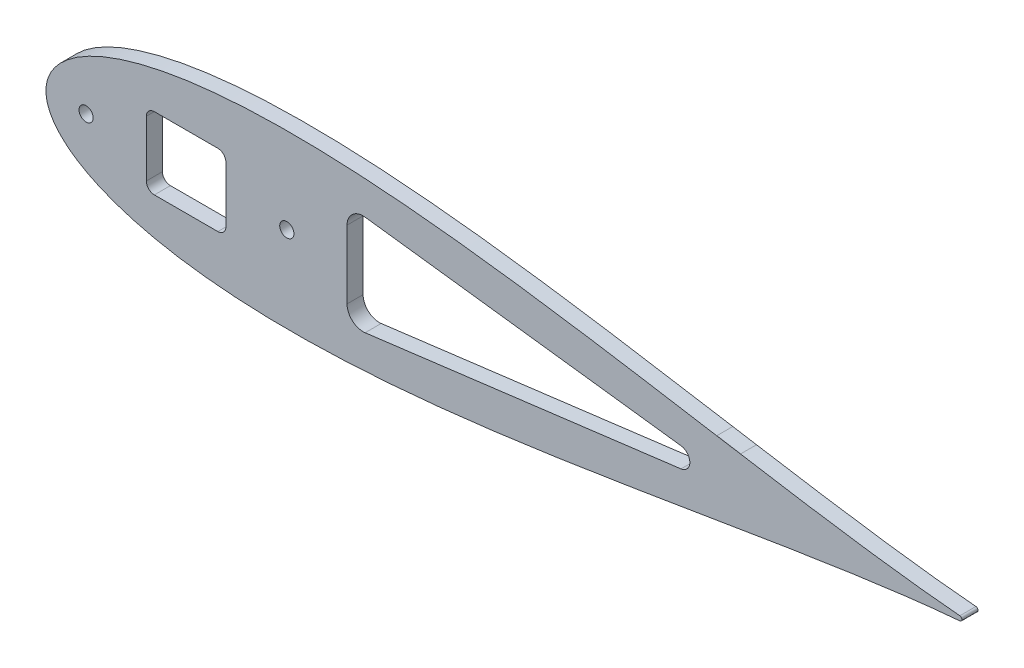
SolidWorks part; units mm, degrees
material "PC High Viscosity"
ref_plane "Front Plane" through (0, 0, 0) normal (0, 0, 1) x (1, 0, 0)
ref_plane "Top Plane" through (0, 0, 0) normal (0, 1, 0) x (1, 0, 0)
ref_plane "Right Plane" through (0, 0, 0) normal (1, 0, 0) x (0, 0, -1)
curve "Curve4"
  spline degree 3 poles (100, 0, 0) (99.8498, 0.0023, 0) (99.4759, 0.008, 0) (99.1023, 0.0238, 0) (98.8789, 0.0332, 0) knots 0 0 0 0 0.401829 1 1 1 1
curve "Curve5"
  spline degree 3 poles (99.3714, -0.0082, 0) (100.2526, 0, 0) (99.3714, 0.0082, 0) (98.8504, 0.035, 0) (97.904, 0.0811, 0) (96.8285, 0.1543, 0) (95.5159, 0.2583, 0) (94.013, 0.3972, 0) (92.313, 0.574, 0) (90.4281, 0.791, 0) (88.3655, 1.0495, 0) (86.1348, 1.3497, 0) (83.7456, 1.691, 0) (81.2082, 2.0715, 0) (78.5335, 2.4886, 0) (75.7326, 2.9386, 0) (72.8172, 3.4168, 0) (69.799, 3.9177, 0) (66.6904, 4.435, 0) (63.5039, 4.9616, 0) (60.2521, 5.4899, 0) (56.948, 6.0119, 0) (53.6049, 6.519, 0) (50.2363, 7.0024, 0) (46.8558, 7.4534, 0) (43.4774, 7.8632, 0) (40.1152, 8.2232, 0) (36.7837, 8.5249, 0) (33.4975, 8.7606, 0) (30.2716, 8.923, 0) (27.1211, 9.0055, 0) (24.0614, 9.0025, 0) (21.108, 8.909, 0) (18.277, 8.7213, 0) (15.5843, 8.4369, 0) (13.0466, 8.0543, 0) (10.6806, 7.5735, 0) (8.5039, 6.996, 0) (6.5349, 6.3253, 0) (4.7933, 5.5673, 0) (3.3001, 4.7321, 0) (2.0777, 3.8366, 0) (1.1467, 2.91, 0) (0.5165, 2.0014, 0) (0.165, 1.1816, 0) (0.0231, 0.524, 0) (-0.0093, 0, 0) (0.0231, -0.524, 0) (0.165, -1.1816, 0) (0.5165, -2.0014, 0) (1.1467, -2.91, 0) (2.0777, -3.8366, 0) (3.3001, -4.7321, 0) (4.7933, -5.5673, 0) (6.5349, -6.3253, 0) (8.5039, -6.996, 0) (10.6806, -7.5735, 0) (13.0466, -8.0543, 0) (15.5843, -8.4369, 0) (18.277, -8.7213, 0) (21.108, -8.909, 0) (24.0614, -9.0025, 0) (27.1211, -9.0055, 0) (30.2716, -8.923, 0) (33.4975, -8.7606, 0) (36.7837, -8.5249, 0) (40.1152, -8.2232, 0) (43.4774, -7.8632, 0) (46.8558, -7.4534, 0) (50.2363, -7.0024, 0) (53.6049, -6.519, 0) (56.948, -6.0119, 0) (60.2521, -5.4899, 0) (63.5039, -4.9616, 0) (66.6904, -4.435, 0) (69.799, -3.9177, 0) (72.8172, -3.4168, 0) (75.7326, -2.9386, 0) (78.5335, -2.4886, 0) (81.2082, -2.0715, 0) (83.7456, -1.691, 0) (86.1348, -1.3497, 0) (88.3655, -1.0495, 0) (90.4281, -0.791, 0) (92.313, -0.574, 0) (94.013, -0.3972, 0) (95.5159, -0.2583, 0) (96.8285, -0.1543, 0) (97.904, -0.0811, 0) (98.8504, -0.035, 0) (99.3714, -0.0082, 0) (100.2526, 0, 0) (99.3714, 0.0082, 0) knots -0.009667 -0.005395 -0.002168 0 0.002168 0.005395 0.009667 0.014967 0.021271 0.028553 0.036781 0.04592 0.055932 0.066773 0.078397 0.090755 0.103793 0.117456 0.131686 0.146422 0.1616 0.177156 0.193024 0.209135 0.225421 0.241812 0.258238 0.274629 0.290914 0.307025 0.322893 0.338448 0.353626 0.368361 0.38259 0.396253 0.40929 0.421647 0.43327 0.444109 0.454119 0.463255 0.471479 0.478755 0.485052 0.490344 0.49461 0.497833 0.5 0.502167 0.50539 0.509656 0.514948 0.521245 0.528521 0.536745 0.545881 0.555891 0.56673 0.578353 0.59071 0.603747 0.61741 0.631639 0.646374 0.661552 0.677107 0.692975 0.709086 0.725371 0.741762 0.758188 0.774579 0.790865 0.806976 0.822844 0.8384 0.853578 0.868314 0.882544 0.896207 0.909245 0.921603 0.933227 0.944068 0.95408 0.963219 0.971447 0.978729 0.985033 0.990333 0.994605 0.997832 1 1.002168 1.005395 1.009667 periodic
sketch "Sketch2" plane through (0, 0, 0) normal (0, 0, 1) x (1, 0, 0)
  line L0 (642.3793, 0) -> (0, 0) construction
  circle A14 centre (642.3793, 0) radius 1.5875 construction
  arc A15 (642.5108, -1.582) -> (642.5108, 1.582) centre (642.3793, 0) ccw
  spline S2 degree 3 poles (666.3448, -0.0547) (672.2538, 0) (666.3448, 0.0547) (662.8509, 0.2344) (656.505, 0.5436) (649.293, 1.0348) (640.4916, 1.7319) (630.4138, 2.6634) (619.0141, 3.8493) (606.375, 5.3044) (592.5439, 7.0376) (577.5855, 9.0506) (561.5643, 11.3389) (544.5497, 13.8907) (526.6141, 16.6877) (507.8326, 19.7051) (488.2827, 22.9117) (468.0444, 26.2704) (447.1994, 29.739) (425.8316, 33.2703) (404.0263, 36.8132) (381.8707, 40.3133) (359.4533, 43.7135) (336.8645, 46.9554) (314.1962, 49.9798) (291.5418, 52.7277) (268.9963, 55.1412) (246.6566, 57.1646) (224.6209, 58.7452) (202.9892, 59.8341) (181.8631, 60.3875) (161.3458, 60.367) (141.542, 59.7399) (122.5581, 58.4818) (104.5023, 56.5743) (87.485, 54.0089) (71.6197, 50.7848) (57.0237, 46.9125) (43.8205, 42.415) (32.1416, 37.3322) (22.1291, 31.7315) (13.9324, 25.7264) (7.6896, 19.5132) (3.4631, 13.4204) (1.1063, 7.9234) (0.1546, 3.5138) (-0.0622, 0) (0.1546, -3.5138) (1.1063, -7.9234) (3.4631, -13.4204) (7.6896, -19.5132) (13.9324, -25.7264) (22.1291, -31.7315) (32.1416, -37.3322) (43.8205, -42.415) (57.0237, -46.9125) (71.6197, -50.7848) (87.485, -54.0089) (104.5023, -56.5743) (122.5581, -58.4818) (141.542, -59.7399) (161.3458, -60.367) (181.8631, -60.3875) (202.9892, -59.8341) (224.6209, -58.7452) (246.6566, -57.1646) (268.9963, -55.1412) (291.5418, -52.7277) (314.1962, -49.9798) (336.8645, -46.9554) (359.4533, -43.7135) (381.8707, -40.3133) (404.0263, -36.8132) (425.8316, -33.2703) (447.1994, -29.739) (468.0444, -26.2704) (488.2827, -22.9117) (507.8326, -19.7051) (526.6141, -16.6877) (544.5497, -13.8907) (561.5643, -11.3389) (577.5855, -9.0506) (592.5439, -7.0376) (606.375, -5.3044) (619.0141, -3.8493) (630.4138, -2.6634) (640.4916, -1.7319) (649.293, -1.0348) (656.505, -0.5436) (662.8509, -0.2344) (666.3448, -0.0547) (672.2538, 0) (666.3448, 0.0547) knots -0.009667 -0.005395 -0.002168 0 0.002168 0.005395 0.009667 0.014967 0.021271 0.028553 0.036781 0.04592 0.055932 0.066773 0.078397 0.090755 0.103793 0.117456 0.131686 0.146422 0.1616 0.177156 0.193024 0.209135 0.225421 0.241812 0.258238 0.274629 0.290914 0.307025 0.322893 0.338448 0.353626 0.368361 0.38259 0.396253 0.40929 0.421647 0.43327 0.444109 0.454119 0.463255 0.471479 0.478755 0.485052 0.490344 0.49461 0.497833 0.5 0.502167 0.50539 0.509656 0.514948 0.521245 0.528521 0.536745 0.545881 0.555891 0.56673 0.578353 0.59071 0.603747 0.61741 0.631639 0.646374 0.661552 0.677107 0.692975 0.709086 0.725371 0.741762 0.758188 0.774579 0.790865 0.806976 0.822844 0.8384 0.853578 0.868314 0.882544 0.896207 0.909245 0.921603 0.933227 0.944068 0.95408 0.963219 0.971447 0.978729 0.985033 0.990333 0.994605 0.997832 1 1.002168 1.005395 1.009667 only from (670.56, 0) to (670.56, 0)
  point P8 (1.2169, -4.6585)
  point P10 (1.2169, 4.6585)
  dimension "D10" = 3.175
extrude "Boss-Extrude1" add sketch "Sketch2" along normal blind 5.4737
extrude "Cut-Extrude4" [suppressed] cut sketch "Sketch7" against normal through all
sketch "Sketch7" plane through (327.9592, -13.7514, 6.35) normal (0, 0, 1) x (1, 0, 0)
  line L1 (-154.9852, -16.7286) -> (-66.0852, -16.7286)
  line L2 (-154.9852, -16.7286) -> (-154.9852, 44.2314)
  line L3 (-154.9852, 44.2314) -> (-66.0852, 44.2314)
  line L4 (-66.0852, -16.7286) -> (-66.0852, 44.2314)
  line L5 (-154.9852, -16.7286) -> (-66.0852, 44.2314) construction
  line L6 (-154.9852, 44.2314) -> (-66.0852, -16.7286) construction
  point P0 (-110.5352, 13.7514)
extrude "Cut-Extrude5" [suppressed] cut sketch "Sketch8" against normal through all
sketch "Sketch8" plane through (327.9592, -13.7514, 6.35) normal (0, 0, 1) x (1, 0, 0)
  circle A0 centre (314.9285, 13.7514) radius 1.2446
scale "Scale1" scale about origin uniform scaling yes scale factor 0.45
sketch "Sketch13" plane through (0, 0, 0) normal (0, 0, 1) x (1, 0, 0)
  arc A1 (289.1299, -0.7119) -> (289.1299, 0.7119) centre (289.0707, 0) ccw
  arc A2 (289.1299, -0.7119) -> (289.1299, 0.7119) centre (289.0707, 0) ccw
  spline S1 degree 3 poles (-1702.4921, 181.9514) (419.1189, 6.2868) (346.4621, -4.6037) (283.6862, 1.1985) (278.5564, 1.7322) (272.8687, 2.387) (266.6448, 3.1669) (259.9135, 4.0728) (252.7039, 5.1025) (245.0474, 6.2508) (236.9764, 7.5095) (228.5247, 8.8673) (219.7272, 10.3103) (210.62, 11.8217) (201.2397, 13.3826) (191.6242, 14.9716) (181.8118, 16.5659) (171.8418, 18.141) (161.754, 19.6711) (151.589, 21.13) (141.3883, 22.4909) (131.1938, 23.7275) (121.0483, 24.8135) (110.9955, 25.7241) (101.0794, 26.4353) (91.3451, 26.9254) (81.8384, 27.1744) (72.6056, 27.1651) (63.6939, 26.883) (55.1511, 26.3168) (47.026, 25.4584) (39.3683, 24.304) (32.2289, 22.8531) (25.6607, 21.1106) (19.7192, 19.0868) (14.4637, 16.7995) (9.9581, 14.2792) (6.2696, 11.5769) (3.4603, 8.7809) (1.5584, 6.0392) (0.4978, 3.5655) (0.0696, 1.5812) (-0.028, 0) (0.0696, -1.5812) (0.4978, -3.5655) (1.5584, -6.0392) (3.4603, -8.7809) (6.2696, -11.5769) (9.9581, -14.2792) (14.4637, -16.7995) (19.7192, -19.0868) (25.6607, -21.1106) (32.2289, -22.8531) (39.3683, -24.304) (47.026, -25.4584) (55.1511, -26.3168) (63.6939, -26.883) (72.6056, -27.1651) (81.8384, -27.1744) (91.3451, -26.9254) (101.0794, -26.4353) (110.9955, -25.7241) (121.0483, -24.8135) (131.1938, -23.7275) (141.3883, -22.4909) (151.589, -21.13) (161.754, -19.6711) (171.8418, -18.141) (181.8118, -16.5659) (191.6242, -14.9716) (201.2397, -13.3826) (210.62, -11.8217) (219.7272, -10.3103) (228.5247, -8.8673) (236.9764, -7.5095) (245.0474, -6.2508) (252.7039, -5.1025) (259.9135, -4.0728) (266.6448, -3.1669) (272.8687, -2.387) (278.5564, -1.7322) (283.6862, -1.1985) (346.4603, 4.6036) (419.1148, -6.2862) (-1702.3066, -181.9361) knots -0.26518 -0.26518 -0.26518 -0.26518 0.021271 0.028553 0.036781 0.04592 0.055932 0.066773 0.078397 0.090755 0.103793 0.117456 0.131686 0.146422 0.1616 0.177156 0.193024 0.209135 0.225421 0.241812 0.258238 0.274629 0.290914 0.307025 0.322893 0.338448 0.353626 0.368361 0.38259 0.396253 0.40929 0.421647 0.43327 0.444109 0.454119 0.463255 0.471479 0.478755 0.485052 0.490344 0.49461 0.497833 0.5 0.502167 0.50539 0.509656 0.514948 0.521245 0.528521 0.536745 0.545881 0.555891 0.56673 0.578353 0.59071 0.603747 0.61741 0.631639 0.646374 0.661552 0.677107 0.692975 0.709086 0.725371 0.741762 0.758188 0.774579 0.790865 0.806976 0.822844 0.8384 0.853578 0.868314 0.882544 0.896207 0.909245 0.921603 0.933227 0.944068 0.95408 0.963219 0.971447 0.978729 1.265171 1.265171 1.265171 1.265171 only from (289.1299, 0.7119) to (289.1299, -0.7119)
  spline S2 degree 3 poles (289.1299, 0.7119) (288.897, 0.7313) (287.1422, 0.8791) (283.6862, 1.1985) (278.5564, 1.7322) (272.8687, 2.387) (266.6448, 3.1669) (259.9135, 4.0728) (252.7039, 5.1025) (245.0474, 6.2508) (236.9764, 7.5095) (228.5247, 8.8673) (219.7272, 10.3103) (210.62, 11.8217) (201.2397, 13.3826) (191.6242, 14.9716) (181.8118, 16.5659) (171.8418, 18.141) (161.754, 19.6711) (151.589, 21.13) (141.3883, 22.4909) (131.1938, 23.7275) (121.0483, 24.8135) (110.9955, 25.7241) (101.0794, 26.4353) (91.3451, 26.9254) (81.8384, 27.1744) (72.6056, 27.1651) (63.6939, 26.883) (55.1511, 26.3168) (47.026, 25.4584) (39.3683, 24.304) (32.2289, 22.8531) (25.6607, 21.1106) (19.7192, 19.0868) (14.4637, 16.7995) (9.9581, 14.2792) (6.2696, 11.5769) (3.4603, 8.7809) (1.5584, 6.0392) (0.4978, 3.5655) (0.0696, 1.5812) (-0.028, 0) (0.0696, -1.5812) (0.4978, -3.5655) (1.5584, -6.0392) (3.4603, -8.7809) (6.2696, -11.5769) (9.9581, -14.2792) (14.4637, -16.7995) (19.7192, -19.0868) (25.6607, -21.1106) (32.2289, -22.8531) (39.3683, -24.304) (47.026, -25.4584) (55.1511, -26.3168) (63.6939, -26.883) (72.6056, -27.1651) (81.8384, -27.1744) (91.3451, -26.9254) (101.0794, -26.4353) (110.9955, -25.7241) (121.0483, -24.8135) (131.1938, -23.7275) (141.3883, -22.4909) (151.589, -21.13) (161.754, -19.6711) (171.8418, -18.141) (181.8118, -16.5659) (191.6242, -14.9716) (201.2397, -13.3826) (210.62, -11.8217) (219.7272, -10.3103) (228.5247, -8.8673) (236.9764, -7.5095) (245.0474, -6.2508) (252.7039, -5.1025) (259.9135, -4.0728) (266.6448, -3.1669) (272.8687, -2.387) (278.5564, -1.7322) (283.6862, -1.1985) (287.1422, -0.8791) (288.897, -0.7313) (289.1299, -0.7119) knots 0.020157 0.020157 0.020157 0.020157 0.021271 0.028553 0.036781 0.04592 0.055932 0.066773 0.078397 0.090755 0.103793 0.117456 0.131686 0.146422 0.1616 0.177156 0.193024 0.209135 0.225421 0.241812 0.258238 0.274629 0.290914 0.307025 0.322893 0.338448 0.353626 0.368361 0.38259 0.396253 0.40929 0.421647 0.43327 0.444109 0.454119 0.463255 0.471479 0.478755 0.485052 0.490344 0.49461 0.497833 0.5 0.502167 0.50539 0.509656 0.514948 0.521245 0.528521 0.536745 0.545881 0.555891 0.56673 0.578353 0.59071 0.603747 0.61741 0.631639 0.646374 0.661552 0.677107 0.692975 0.709086 0.725371 0.741762 0.758188 0.774579 0.790865 0.806976 0.822844 0.8384 0.853578 0.868314 0.882544 0.896207 0.909245 0.921603 0.933227 0.944068 0.95408 0.963219 0.971447 0.978729 0.979843 0.979843 0.979843 0.979843
  dimension "D1" = 0
extrude "Boss-Extrude2" add sketch "Sketch13" along normal blind 5.08
sketch "Sketch10" plane through (0, 0, 5.08) normal (0, 0, 1) x (1, 0, 0)
  line L1 (31.75, -11.4046) -> (56.9172, -11.4046)
  line L2 (31.75, -11.4046) -> (31.75, 11.4046)
  line L3 (31.75, 11.4046) -> (56.9172, 11.4046)
  line L4 (56.9172, -11.4046) -> (56.9172, 11.4046)
  line L5 (31.75, -11.4046) -> (56.9172, 11.4046) construction
  line L6 (31.75, 11.4046) -> (56.9172, -11.4046) construction
  point P0 (44.3336, 0)
  dimension "D2" = 31.75
  dimension "D5" = 22.8092
  dimension "D1" = 25.1672
extrude "Cut-Extrude6" cut sketch "Sketch10" against normal through all
sketch "Sketch11" [suppressed] plane through (0, 0, 2.2225) normal (0, 0, 1) x (1, 0, 0)
  line L1 (22.225, 9.525) -> (41.275, 9.525)
  line L2 (22.225, 9.525) -> (22.225, -9.525)
  line L3 (22.225, -9.525) -> (41.275, -9.525)
  line L4 (41.275, 9.525) -> (41.275, -9.525)
  line L5 (22.225, 9.525) -> (41.275, -9.525) construction
  line L6 (22.225, -9.525) -> (41.275, 9.525) construction
  point P0 (31.75, 0)
  dimension "D1" = 19.05
  dimension "D2" = 22.225
extrude "Cut-Extrude7" [suppressed] cut sketch "Sketch11" against normal through all
sketch "Sketch12" [suppressed] plane through (0, 0, 0) normal (0, 0, 1) x (1, 0, 0)
  line L1 (114.3, -9.525) -> (133.35, -9.525)
  line L2 (114.3, -9.525) -> (114.3, 9.525)
  line L3 (114.3, 9.525) -> (133.35, 9.525)
  line L4 (133.35, -9.525) -> (133.35, 9.525)
  line L5 (114.3, -9.525) -> (133.35, 9.525) construction
  line L6 (114.3, 9.525) -> (133.35, -9.525) construction
  point P0 (123.825, 0)
  dimension "D1" = 19.05
  dimension "D2" = 114.3
extrude "Cut-Extrude10" [suppressed] cut sketch "Sketch12" along normal blind 2.54
fillet "Fillet1" radius 2.54 4 edges at (56.9172, 11.4046, 2.54) (56.9172, -11.4046, 2.54) (31.75, -11.4046, 2.54) (31.75, 11.4046, 2.54)
hole_wizard " Tapped Hole1" [suppressed] positions "3DSketch1" profile "Sketch15" tap size "#8-32" standard "ANSI Inch"
sketch3d "3DSketch1"
  line L0 (215.9, 11.9855, 2.54) -> (215.9, -11.9855, 2.54) construction
  line L1 (0, 0, 0) -> (0, 0, 2.54) construction
  line L2 (215.9, -11.9855, 0) -> (215.9, -11.9855, 2.54) construction
  spline S5 degree 3 poles (295.555, 0.7277, 0) (295.317, 0.7475, 0) (293.5231, 0.8986, 0) (289.9904, 1.2252, 0) (284.7465, 1.7707, 0) (278.9325, 2.44, 0) (272.5702, 3.2373, 0) (265.6893, 4.1633, 0) (258.3196, 5.2159, 0) (250.4929, 6.3897, 0) (242.2425, 7.6764, 0) (233.603, 9.0644, 0) (224.61, 10.5394, 0) (215.3004, 12.0844, 0) (205.7117, 13.6799, 0) (195.8825, 15.3043, 0) (185.8521, 16.9341, 0) (175.6605, 18.5441, 0) (165.3485, 20.1082, 0) (154.9577, 21.5995, 0) (144.5303, 22.9907, 0) (134.1092, 24.2547, 0) (123.7383, 25.365, 0) (113.462, 26.2957, 0) (103.3256, 27.0228, 0) (93.375, 27.5237, 0) (83.657, 27.7783, 0) (74.2191, 27.7688, 0) (65.1093, 27.4804, 0) (56.3767, 26.9016, 0) (48.0711, 26.0242, 0) (40.2431, 24.8441, 0) (32.9451, 23.361, 0) (26.2309, 21.5798, 0) (20.1574, 19.5109, 0) (14.7852, 17.1728, 0) (10.1794, 14.5965, 0) (6.4089, 11.8341, 0) (3.5372, 8.9761, 0) (1.593, 6.1734, 0) (0.5089, 3.6448, 0) (0.0711, 1.6163, 0) (-0.0286, 0, 0) (0.0711, -1.6163, 0) (0.5089, -3.6448, 0) (1.593, -6.1734, 0) (3.5372, -8.9761, 0) (6.4089, -11.8341, 0) (10.1794, -14.5965, 0) (14.7852, -17.1728, 0) (20.1574, -19.5109, 0) (26.2309, -21.5798, 0) (32.9451, -23.361, 0) (40.2431, -24.8441, 0) (48.0711, -26.0242, 0) (56.3767, -26.9016, 0) (65.1093, -27.4804, 0) (74.2191, -27.7688, 0) (83.657, -27.7783, 0) (93.375, -27.5237, 0) (103.3256, -27.0228, 0) (113.462, -26.2957, 0) (123.7383, -25.365, 0) (134.1092, -24.2547, 0) (144.5303, -22.9907, 0) (154.9577, -21.5995, 0) (165.3485, -20.1082, 0) (175.6605, -18.5441, 0) (185.8521, -16.9341, 0) (195.8825, -15.3043, 0) (205.7117, -13.6799, 0) (215.3004, -12.0844, 0) (224.61, -10.5394, 0) (233.603, -9.0644, 0) (242.2425, -7.6764, 0) (250.4929, -6.3897, 0) (258.3196, -5.2159, 0) (265.6893, -4.1633, 0) (272.5702, -3.2373, 0) (278.9325, -2.44, 0) (284.7465, -1.7707, 0) (289.9904, -1.2252, 0) (293.5231, -0.8986, 0) (295.317, -0.7475, 0) (295.555, -0.7277, 0) knots 0 0 0 0 0.001161 0.008748 0.017322 0.026845 0.037278 0.048574 0.060687 0.073563 0.087149 0.101387 0.116214 0.131569 0.147385 0.163594 0.180128 0.196916 0.213886 0.230966 0.248082 0.265161 0.282131 0.298919 0.315453 0.331662 0.347477 0.362831 0.377658 0.391895 0.40548 0.418356 0.430467 0.441761 0.452191 0.461711 0.470281 0.477863 0.484424 0.489938 0.494383 0.497742 0.5 0.502258 0.505617 0.510062 0.515576 0.522137 0.529719 0.538289 0.547809 0.558239 0.569533 0.581644 0.59452 0.608105 0.622342 0.637169 0.652523 0.668338 0.684547 0.701081 0.717869 0.734839 0.751918 0.769034 0.786114 0.803084 0.819872 0.836406 0.852615 0.868431 0.883786 0.898613 0.912851 0.926437 0.939313 0.951426 0.962722 0.973155 0.982678 0.991252 0.998839 1 1 1 1 construction
  point P0 (0, 0, 2.54)
  point P3 (215.9, -11.9855, 2.54)
  point P5 (215.9, 11.9855, 2.54)
  point P64 (0, 0, 2.54)
  dimension "D1" = 215.9
  dimension "D2" = 2.54
  dimension "D3" = 2.54
sketch "Sketch15" plane through (215.9, 11.9855, 2.54) normal (0, 0, 1) x (-0.9865, 0.1639, 0)
  line L0 (0, 0) -> (0, 9.4198)
  line L1 (0, 9.4198) -> (1.7272, 8.382)
  line L2 (1.7272, 8.382) -> (1.7272, 0)
  line L5 (1.7272, 0) -> (0, 0)
  line L10 (0, 9.4198) -> (-1.7272, 8.382) construction
  line L11 (0, -6.35) -> (0, 107.95) construction
  dimension "Tap Drill Dia." = 3.4544
  dimension "Tap Drill Depth" = 8.382
  dimension "Drill Angle" = 118
cosmetic thread "Hole Thread6" [suppressed] parameters "D1"=0, "D2"=4.4544
cosmetic thread "Hole Thread7" [suppressed] parameters "D1"=0, "D2"=4.4544
hole_wizard "#8-32 Tapped Hole2" [suppressed] positions "3DSketch2" profile "Sketch16" tap size "#8-32" standard "ANSI Inch"
sketch3d "3DSketch2"
  line L0 (0, 0, 0) -> (0.0007, -0.1233, 2.621) construction
  point P0 (0.0007, -0.1233, 2.621)
sketch "Sketch16" plane through (0.0007, -0.1233, 2.621) normal (0, 0, 1) x (0.0109, -0.9999, 0)
  line L0 (0, 0) -> (0, 11.7058)
  line L1 (0, 11.7058) -> (1.7272, 10.668)
  line L2 (1.7272, 10.668) -> (1.7272, 0)
  line L5 (1.7272, 0) -> (0, 0)
  line L10 (0, 11.7058) -> (-1.7272, 10.668) construction
  line L11 (0, -6.35) -> (0, 107.95) construction
  dimension "Tap Drill Dia." = 3.4544
  dimension "Tap Drill Depth" = 10.668
  dimension "Drill Angle" = 118
cosmetic thread "Hole Thread8" [suppressed] parameters "D1"=0, "D2"=4.4544
sketch "Sketch18" plane through (0, 0, 0) normal (0, 1, 0) x (1, 0, 0)
  line L1 (212.2041, -4.9774) -> (219.7159, -4.9774)
  line L2 (212.2041, -4.9774) -> (212.2041, 0)
  line L3 (212.2041, 0) -> (219.7159, 0)
  line L4 (219.7159, -4.9774) -> (219.7159, 0)
split line "Split Line1"
hole_wizard "#8 Clearance Hole1" positions "Sketch19" profile "Sketch20" hole size "#8" standard "ANSI Inch" end condition through all
sketch "Sketch19" plane through (0, 0, 5.08) normal (0, 0, 1) x (1, 0, 0)
  line L0 (0, 0) -> (76.2, 0) construction
  line L2 (31.75, 8.8646) -> (31.75, -8.8646) construction
  point P0 (76.2, 0)
  point P2 (12.7, 0)
  dimension "D1" = 19.05
  dimension "D2" = 44.45
sketch "Sketch20" plane through (76.2, 0, 5.08) normal (1, 0, 0) x (0, -1, 0)
  line L0 (0, 0) -> (0, 5.08)
  line L1 (0, 5.08) -> (2.2479, 5.08)
  line L2 (2.2479, 5.08) -> (2.2479, 0)
  line L5 (2.2479, 0) -> (0, 0)
  line L11 (0, -6.35) -> (0, 107.95) construction
  dimension "Thru Hole Dia." = 4.4958
  dimension "Thru Hole Depth" = 5.08
sketch "Sketch21" plane through (0, 0, 0) normal (0, 0, -1) x (-1, 0, 0)
  line L0 (-95.25, -16.5582) -> (-95.25, 16.5582)
  line L1 (-95.25, 16.5582) -> (-203.6955, 2.8132)
  line L2 (-203.6955, 2.8132) -> (-203.6955, -2.8132)
  line L3 (-203.6955, -2.8132) -> (-95.25, -16.5582)
  line L4 (-95.25, 0) -> (-203.6955, 0) construction
  line L5 (-56.9172, -8.8646) -> (-56.9172, 8.8646) construction
  circle A0 centre (-76.2, 0) radius 2.2479 construction
  spline S0 degree 3 poles (-212.2041, 11.5592) (-211.7065, 11.6418) (-208.0776, 12.2447) (-201.2397, 13.3826) (-191.6242, 14.9716) (-181.8118, 16.5659) (-171.8418, 18.141) (-161.754, 19.6711) (-151.589, 21.13) (-141.3883, 22.4909) (-131.1938, 23.7275) (-121.0483, 24.8135) (-110.9955, 25.7241) (-101.0794, 26.4353) (-91.3451, 26.9254) (-81.8384, 27.1744) (-72.6056, 27.1651) (-63.6939, 26.883) (-55.1511, 26.3168) (-47.026, 25.4584) (-39.3683, 24.304) (-32.2289, 22.8531) (-25.6607, 21.1106) (-19.7192, 19.0868) (-14.4637, 16.7995) (-9.9581, 14.2792) (-6.2696, 11.5769) (-3.4603, 8.7809) (-1.5584, 6.0392) (-0.4978, 3.5655) (-0.0696, 1.5812) (0.028, 0) (-0.0696, -1.5812) (-0.4978, -3.5655) (-1.5584, -6.0392) (-3.4603, -8.7809) (-6.2696, -11.5769) (-9.9581, -14.2792) (-14.4637, -16.7995) (-19.7192, -19.0868) (-25.6607, -21.1106) (-32.2289, -22.8531) (-39.3683, -24.304) (-47.026, -25.4584) (-55.1511, -26.3168) (-63.6939, -26.883) (-72.6056, -27.1651) (-81.8384, -27.1744) (-91.3451, -26.9254) (-101.0794, -26.4353) (-110.9955, -25.7241) (-121.0483, -24.8135) (-131.1938, -23.7275) (-141.3883, -22.4909) (-151.589, -21.13) (-161.754, -19.6711) (-171.8418, -18.141) (-181.8118, -16.5659) (-191.6242, -14.9716) (-201.2397, -13.3826) (-208.0776, -12.2447) (-211.7065, -11.6418) (-212.2041, -11.5592) knots 0.14401 0.14401 0.14401 0.14401 0.146422 0.1616 0.177156 0.193024 0.209135 0.225421 0.241812 0.258238 0.274629 0.290914 0.307025 0.322893 0.338448 0.353626 0.368361 0.38259 0.396253 0.40929 0.421647 0.43327 0.444109 0.454119 0.463255 0.471479 0.478755 0.485052 0.490344 0.49461 0.497833 0.5 0.502167 0.50539 0.509656 0.514948 0.521245 0.528521 0.536745 0.545881 0.555891 0.56673 0.578353 0.59071 0.603747 0.61741 0.631639 0.646374 0.661552 0.677107 0.692975 0.709086 0.725371 0.741762 0.758188 0.774579 0.790865 0.806976 0.822844 0.8384 0.853578 0.85599 0.85599 0.85599 0.85599 construction
  spline S2 degree 3 poles (-219.7159, -10.315) (-219.7546, -10.3086) (-222.7295, -9.8178) (-228.5247, -8.8673) (-236.9764, -7.5095) (-245.0474, -6.2508) (-252.7039, -5.1025) (-259.9135, -4.0728) (-266.6448, -3.1669) (-272.8687, -2.387) (-278.5564, -1.7322) (-283.6862, -1.1985) (-287.1422, -0.8791) (-288.897, -0.7313) (-289.1299, -0.7119) knots 0.868126 0.868126 0.868126 0.868126 0.868314 0.882544 0.896207 0.909245 0.921603 0.933227 0.944068 0.95408 0.963219 0.971447 0.978729 0.979843 0.979843 0.979843 0.979843 construction
  spline S3 degree 3 poles (-289.1299, 0.7119) (-288.897, 0.7313) (-287.1422, 0.8791) (-283.6862, 1.1985) (-278.5564, 1.7322) (-272.8687, 2.387) (-266.6448, 3.1669) (-259.9135, 4.0728) (-252.7039, 5.1025) (-245.0474, 6.2508) (-236.9764, 7.5095) (-228.5247, 8.8673) (-222.7295, 9.8178) (-219.7546, 10.3086) (-219.7159, 10.315) knots 0.020157 0.020157 0.020157 0.020157 0.021271 0.028553 0.036781 0.04592 0.055932 0.066773 0.078397 0.090755 0.103793 0.117456 0.131686 0.131874 0.131874 0.131874 0.131874 construction
  point P6 (-203.6955, -12.9732)
  point P9 (-56.9172, 0)
  point P10 (-95.25, -26.7182)
  point P11 (-222.7455, -9.8162)
  point P14 (-222.7455, 9.8162)
  dimension "D1" = 19.05
  dimension "D2" = 10.16
  dimension "D3" = 10.16
  dimension "D5" = 19.05
  dimension "D4" = 19.6324
extrude "Cut-Extrude11" cut sketch "Sketch21" against normal through all
fillet "Fillet2" radius 5.08 2 edges at (95.25, 16.5582, 2.54) (95.25, -16.5582, 2.54)
fillet "Fillet3" radius 3.1923 4 edges at (203.6955, 0, 5.08) (203.6955, -2.8132, 2.54) (203.6955, 2.8132, 2.54) (203.6955, 0, 0)
equation "\"0.5n\"=0"
equation "\"D3@Sketch21\"=\"D2@Sketch21\""
equation "\"D1@Sketch10\"=0.898/cos(25deg)"
